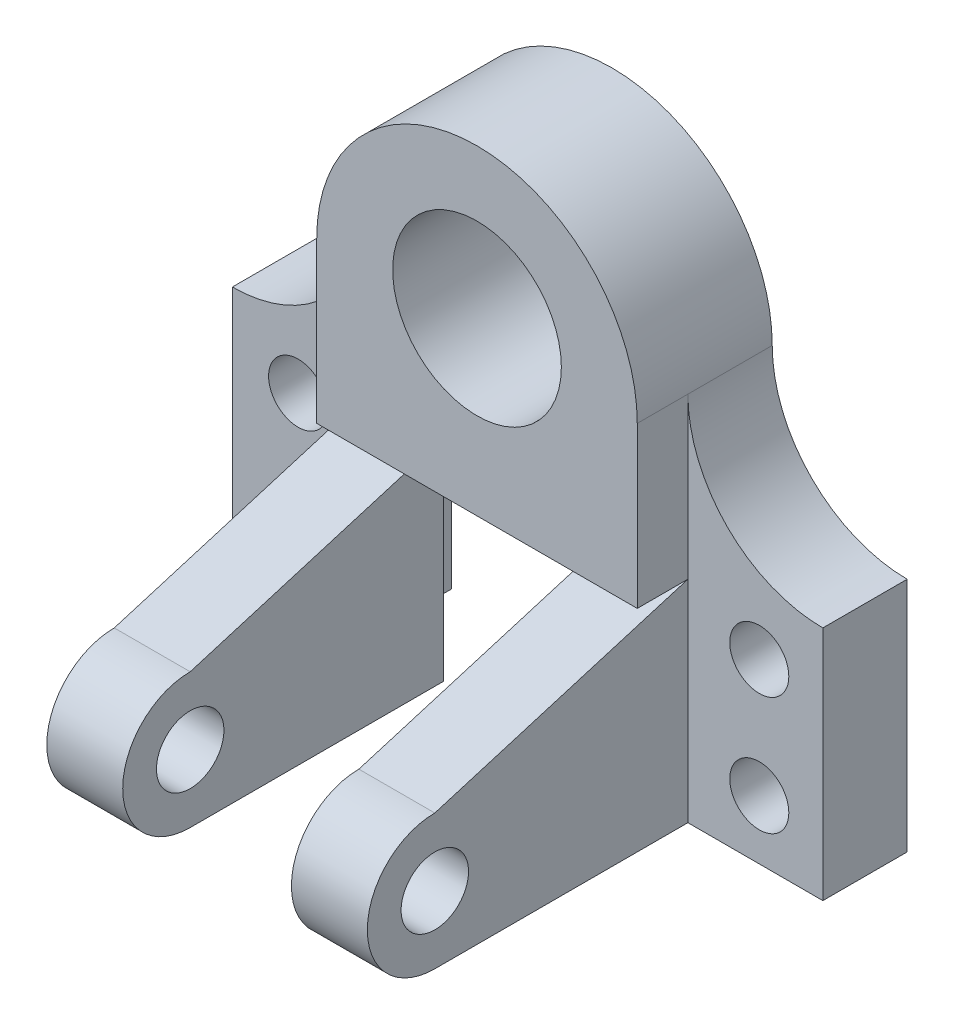
SolidWorks part; units mm, degrees
ref_plane "Front" through (0, 0, 0) normal (0, 0, 1) x (1, 0, 0)
ref_plane "Top" through (0, 0, 0) normal (0, 1, 0) x (1, 0, 0)
ref_plane "Right" through (0, 0, 0) normal (1, 0, 0) x (0, 0, -1)
sketch "Sketch1" plane through (0, 0, 0) normal (0, 0, 1) x (1, 0, 0)
  line L0 (-38, 0) -> (38, 0)
  line L1 (38, 0) -> (38, 38)
  line L3 (-38, 38) -> (-38, 0)
  line L5 (-70, 6) -> (-70, -50)
  line L6 (-70, -50) -> (-38, -50)
  line L7 (-38, -50) -> (-38, 0)
  line L8 (70, -50) -> (38, -50)
  line L9 (70, 6) -> (70, -50)
  line L10 (-38, 0) -> (-38, -50)
  line L11 (38, 0) -> (38, -50)
  arc A0 (-38, 38) -> (38, 38) centre (0, 38) cw
  arc A1 (-38, 38) -> (-70, 6) centre (-70, 38) cw
  arc A2 (38, 38) -> (70, 6) centre (70, 38) ccw
  point P7 (0, 0)
  dimension "D1" = 76
  dimension "D3" = 32
  dimension "D2" = 38
  dimension "D4" = 56
  dimension "D5" = 140
  dimension "D6" = 56
  dimension "D7" = 32
extrude "Boss-Extrude1" add sketch "Sketch1" along normal blind 32 contours A0 L3 L0 L1 region at (0, 34.4527, 0)
extrude "Boss-Extrude2" add sketch "Sketch1<3>" along normal blind 20 contours L3 A1 L5 L6 L7 | A2 L1 L11 L8 L9 region at (-53.033, -18.1607, 0) region at (53.033, -18.1607, 0)
sketch "Sketch1<3>" plane through (0, 0, 0) normal (0, 0, 1) x (1, 0, 0) same geometry as "Sketch1"
sketch "Sketch2" plane through (0, 0, 20) normal (0, 0, 1) x (1, 0, 0)
  circle A0 centre (-54.4144, -8) radius 7
  circle A1 centre (-54.4144, -36) radius 7
  circle A2 centre (54.9294, -8) radius 7
  circle A3 centre (54.9294, -36) radius 7
  dimension "D1" = 28
  dimension "D4" = 14
  dimension "D2" = 14
  dimension "D3" = 14
extrude "Cut-Extrude1" cut sketch "Sketch2" against normal blind 20
sketch "Sketch3" plane through (0, 0, 32) normal (0, 0, 1) x (1, 0, 0)
  circle A0 centre (0, 40.5505) radius 20
  dimension "D1" = 40
extrude "Cut-Extrude3" cut sketch "Sketch3" against normal through all
sketch "Sketch4" plane through (-38, 0, 0) normal (1, 0, 0) x (0, 0, -1)
  line L0 (-20, -50) -> (-80, -50)
  line L1 (-80, -18) -> (-20, 0)
  line L2 (-20, 0) -> (-20, -50)
  arc A0 (-80, -50) -> (-80, -18) centre (-80, -34) cw
  dimension "D1" = 16
  dimension "D2" = 60
extrude "Boss-Extrude3" add sketch "Sketch4" along normal blind 18 separate body
sketch "Sketch5" plane through (38, 0, 0) normal (-1, 0, 0) x (0, 0, 1)
  line L0 (20, -50) -> (80, -50)
  line L1 (20, 0) -> (80, -18)
  line L2 (20, 0) -> (20, -50)
  arc A0 (80, -50) -> (80, -18) centre (80, -34) ccw
  dimension "D1" = 16
  dimension "D2" = 60
extrude "Boss-Extrude4" add sketch "Sketch5" along normal blind 18 separate body
sketch "Sketch6" plane through (-38, 0, 0) normal (-1, 0, 0) x (0, 0, 1)
  circle A0 centre (80, -33.9996) radius 8
  point P2 (81.8535, -33.9996)
  point P3 (0, 0)
  dimension "D1" = 16
extrude "Cut-Extrude4" cut sketch "Sketch6" against normal through all
